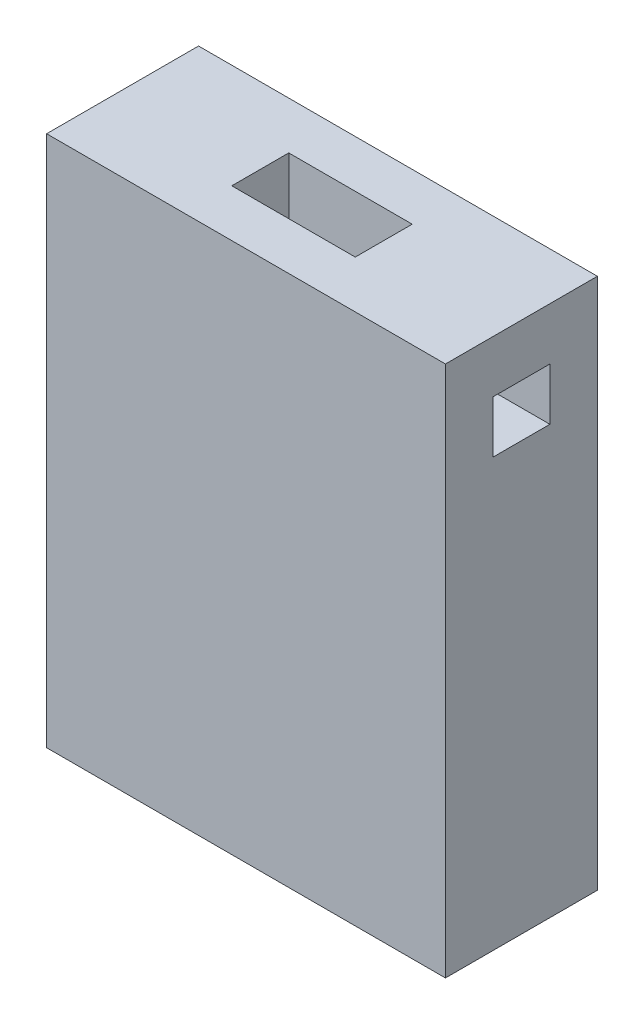
SolidWorks part; units mm, degrees
ref_plane "Plan de face" through (0, 0, 0) normal (0, 0, 1) x (1, 0, 0)
ref_plane "Plan de dessus" through (0, 0, 0) normal (0, 1, 0) x (1, 0, 0)
ref_plane "Plan de droite" through (0, 0, 0) normal (1, 0, 0) x (0, 0, -1)
sketch "Esquisse1" plane through (0, 0, 0) normal (0, 1, 0) x (1, 0, 0)
  line L1 (-21, 8) -> (21, 8)
  line L2 (-21, 8) -> (-21, -8)
  line L3 (-21, -8) -> (21, -8)
  line L4 (21, 8) -> (21, -8)
  line L5 (-21, 8) -> (21, -8) construction
  line L6 (-21, -8) -> (21, 8) construction
  point P0 (0, 0)
  dimension "D1" = 42
  dimension "D2" = 16
extrude "Boss.-Extru.1" add sketch "Esquisse1" along normal blind 56
sketch "Esquisse2" plane through (0, 56, 0) normal (0, 1, 0) x (1, 0, 0)
  line L1 (-6.5, -3) -> (6.5, -3)
  line L2 (-6.5, -3) -> (-6.5, 3)
  line L3 (-6.5, 3) -> (6.5, 3)
  line L4 (6.5, -3) -> (6.5, 3)
  line L5 (-6.5, -3) -> (6.5, 3) construction
  line L6 (-6.5, 3) -> (6.5, -3) construction
  point P0 (0, 0)
  dimension "D1" = 13
  dimension "D2" = 6
extrude "Enlèv. mat.-Extru.1" cut sketch "Esquisse2" against normal blind 11
sketch "Esquisse3" plane through (-6.5, 0, 0) normal (1, 0, 0) x (0, 0, -1)
  line L0 (3, 45) -> (3, 56) construction
  line L1 (-3, 45) -> (3, 45)
  line L2 (-3, 45) -> (-3, 50.5)
  line L3 (-3, 50.5) -> (3, 50.5)
  line L4 (3, 45) -> (3, 50.5)
extrude "Enlèv. mat.-Extru.2" cut sketch "Esquisse3" along normal through all
